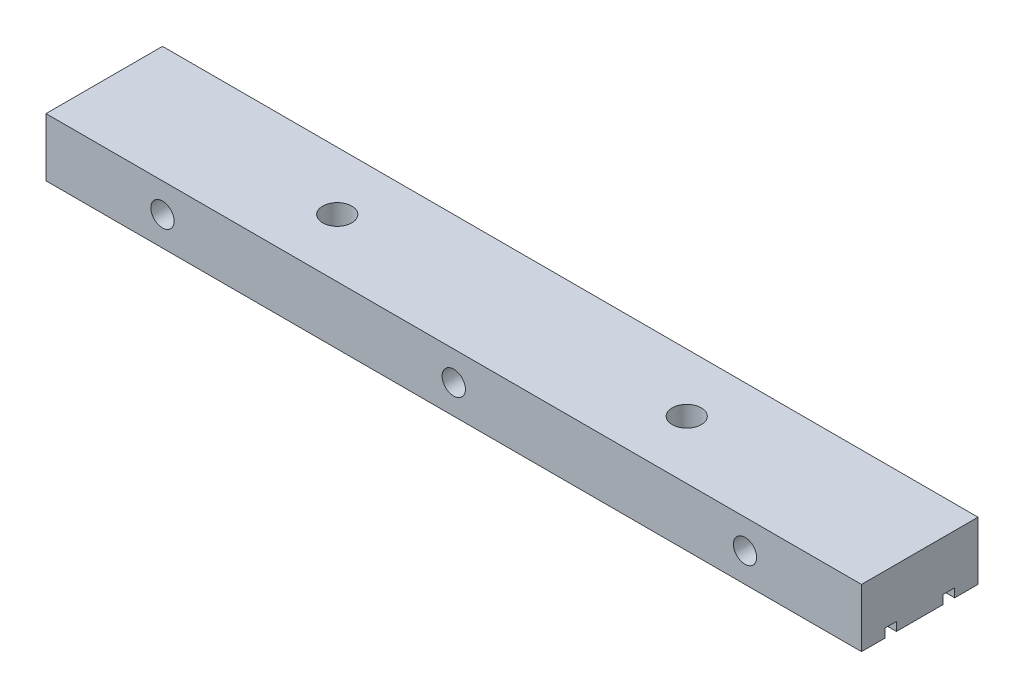
SolidWorks part; units mm, degrees
ref_plane "Ön Düzlem" through (0, 0, 0) normal (0, 0, 1) x (1, 0, 0)
ref_plane "Üst Düzlem" through (0, 0, 0) normal (0, 1, 0) x (1, 0, 0)
ref_plane "Sağ Düzlem" through (0, 0, 0) normal (1, 0, 0) x (0, 0, -1)
sketch "Çizim1" plane through (0, 0, 0) normal (0, 0, 1) x (1, 0, 0)
  line L1 (0, 0) -> (140, 0)
  line L2 (0, 0) -> (0, 10)
  line L3 (0, 10) -> (140, 10)
  line L4 (140, 0) -> (140, 10)
  point P5 (0, 0)
  point P6 (0, 0)
  point P9 (0, 0)
  point P10 (0, 0)
  dimension "D4" = 10
extrude "Yükseklik-Ekstrüzyon1" add sketch "Çizim1" along normal blind 20
sketch "Çizim4" plane through (0, 10, 0) normal (0, 1, 0) x (1, 0, 0)
  line L0 (0, -10) -> (140, -10) construction
  line L1 (0, -20) -> (0, 0) construction
  line L2 (140, -20) -> (140, 0) construction
  line L3 (40, 0) -> (40, -20) construction
  line L4 (140, 0) -> (0, 0) construction
  line L5 (140, -20) -> (0, -20) construction
  line L6 (100, 0) -> (100, -20) construction
  point P16 (40, -10)
  point P17 (100, -10)
  dimension "D1" = 40
  dimension "D2" = 40
hole_wizard "Ø4.0mm Saplama Delikleri1" positions "3B Çizim3" profile "Çizim5" hole size "Ø4.0" standard "ANSI Metric"
sketch3d "3B Çizim3"
  point P0 (40, 10, 10)
  point P3 (100, 10, 10)
sketch "Çizim5" plane through (40, 10, 10) normal (1, 0, 0) x (0, 0, 1)
  line L0 (0, 0) -> (0, 8)
  line L1 (0, 8) -> (2.5, 8)
  line L2 (2.5, 8) -> (2.5, 0)
  line L5 (2.5, 0) -> (0, 0)
  line L10 (0, 8) -> (-2.5, 8) construction
  line L11 (0, -6.35) -> (0, 107.95) construction
  dimension "Hole Dia." = 5
  dimension "Hole Depth" = 8
  dimension "Drill Angle" = 180
sketch "Çizim6" plane through (0, 0, 0) normal (-1, 0, 0) x (0, 0, 1)
  line L0 (20, 0) -> (0, 0) construction
  line L1 (0, 10) -> (0, 0) construction
  line L2 (4, 0) -> (6, 0)
  line L3 (4, 0) -> (4, 1.5)
  line L4 (4, 1.5) -> (6, 1.5)
  line L5 (6, 0) -> (6, 1.5)
  line L6 (14, 0) -> (16, 0)
  line L7 (14, 0) -> (14, 1.5)
  line L8 (14, 1.5) -> (16, 1.5)
  line L9 (16, 0) -> (16, 1.5)
  line L10 (20, 10) -> (20, 0) construction
  dimension "D1" = 4
  dimension "D2" = 4
  dimension "D3" = 2
  dimension "D4" = 2
  dimension "D5" = 1.5
extrude "Kes-Ekstrüzyon1" cut sketch "Çizim6" against normal through all
sketch "Çizim7" plane through (0, 0, 0) normal (0, 0, -1) x (-1, 0, 0)
  line L0 (-140, 5) -> (0, 5) construction
  line L1 (-140, 0) -> (-140, 10) construction
  line L2 (0, 10) -> (0, 0) construction
  point P6 (-120, 5)
  point P7 (-70, 5)
  point P8 (-20, 5)
  dimension "D1" = 20
  dimension "D2" = 20
hole_wizard "M5 Altıgen Başlı Cıvata İçin Havşa1" positions "3B Çizim4" profile "Çizim8" counterbore size "M5" standard "ANSI Metric" end condition through all
sketch3d "3B Çizim4"
  point P0 (120, 5, 0)
  point P3 (70, 5, 0)
  point P6 (20, 5, 0)
sketch "Çizim8" plane through (120, 5, 0) normal (1, 0, 0) x (0, 1, 0)
  line L0 (0, 0) -> (0, 20)
  line L1 (0, 20) -> (2, 20)
  line L3 (2, 20) -> (2, 6)
  line L4 (2, 6) -> (3.25, 6)
  line L5 (3.25, 6) -> (3.25, 0)
  line L7 (3.25, 0) -> (0, 0)
  line L11 (0, -6.35) -> (0, 107.95) construction
  dimension "Thru Hole Dia." = 4
  dimension "Thru Hole Depth" = 20
  dimension "C'Bore Dia." = 6.5
  dimension "C'Bore Depth" = 6
